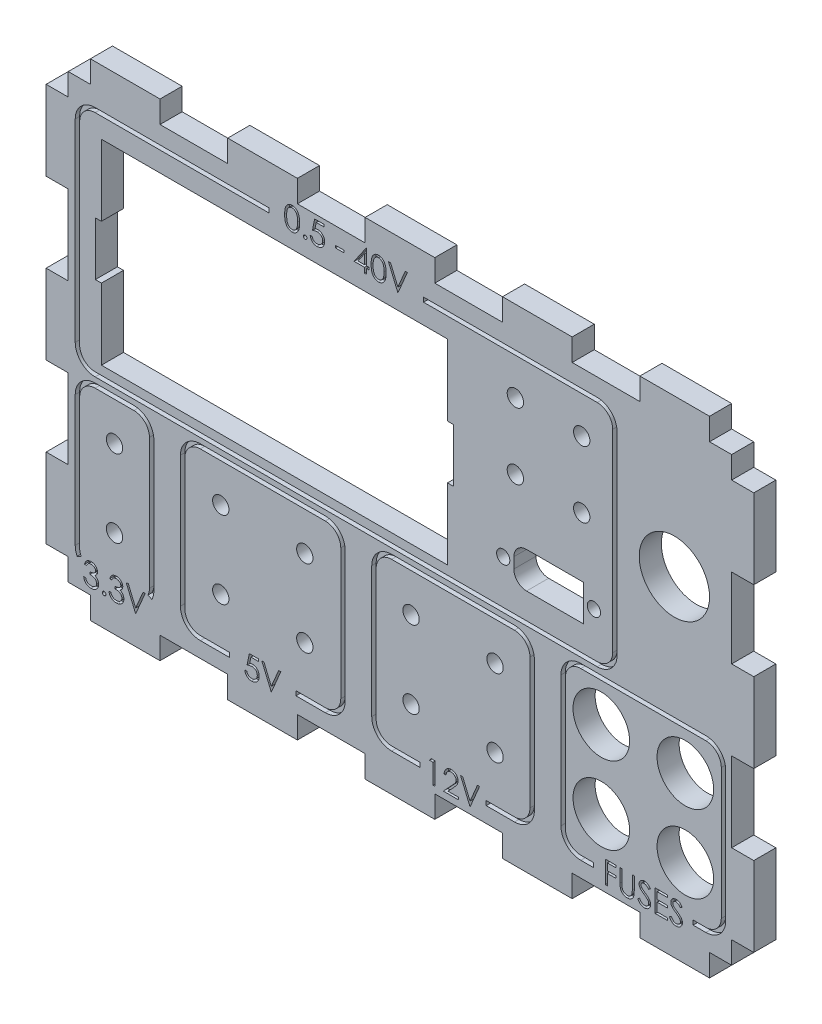
SolidWorks part; units mm, degrees
ref_plane "Front Plane" through (0, 0, 0) normal (0, 0, 1) x (1, 0, 0)
ref_plane "Top Plane" through (0, 0, 0) normal (0, 1, 0) x (1, 0, 0)
ref_plane "Right Plane" through (0, 0, 0) normal (1, 0, 0) x (0, 0, -1)
sketch "Sketch1" plane through (0, 0, 0) normal (0, 0, 1) x (1, 0, 0)
  line L1 (-75, 50) -> (-70, 50)
  line L2 (-75, 50) -> (-75, 45)
  line L3 (-75, -50) -> (-70, -50)
  line L4 (75, 50) -> (75, 45)
  line L5 (-75, 50) -> (75, -50) construction
  line L6 (-75, -50) -> (75, 50) construction
  line L7 (-75, 45) -> (-80, 45)
  line L9 (-75, 27) -> (-80, 27)
  line L10 (-80, 45) -> (-80, 27)
  line L11 (-75, 9) -> (-80, 9)
  line L12 (-80, 9) -> (-80, -9)
  line L13 (-75, -9) -> (-80, -9)
  line L15 (-75, -27) -> (-80, -27)
  line L16 (-80, -27) -> (-80, -45)
  line L17 (-75, -45) -> (-80, -45)
  line L18 (-80, -50) -> (-80, -45) construction
  line L19 (-80, 45) -> (-80, 50) construction
  line L20 (0, 55) -> (0, -55) construction
  line L21 (75, -27) -> (80, -27)
  line L22 (80, -27) -> (80, -45)
  line L23 (75, -45) -> (80, -45)
  line L25 (75, 9) -> (80, 9)
  line L26 (80, 9) -> (80, -9)
  line L27 (75, -9) -> (80, -9)
  line L29 (75, 27) -> (80, 27)
  line L30 (80, 45) -> (80, 27)
  line L31 (75, 45) -> (80, 45)
  line L33 (-38.9375, 50) -> (-38.9375, 55)
  line L35 (-70, 50) -> (-70, 55)
  line L36 (-70, 55) -> (-54.25, 55)
  line L37 (-54.25, 50) -> (-54.25, 55)
  line L39 (-23.1875, 50) -> (-23.1875, 55)
  line L40 (-38.9375, 55) -> (-23.1875, 55)
  line L41 (-7.875, 50) -> (-7.875, 55)
  line L43 (7.875, 50) -> (7.875, 55)
  line L44 (-7.875, 55) -> (7.875, 55)
  line L45 (23.1875, 50) -> (23.1875, 55)
  line L47 (38.9375, 50) -> (38.9375, 55)
  line L48 (23.1875, 55) -> (38.9375, 55)
  line L49 (54.25, 50) -> (54.25, 55)
  line L51 (70, 50) -> (70, 55)
  line L52 (54.25, 55) -> (70, 55)
  line L53 (-70, 55) -> (-75, 55) construction
  line L54 (70, 55) -> (75, 55) construction
  line L55 (-80, 0) -> (80, 0) construction
  line L57 (70, -50) -> (70, -55)
  line L58 (54.25, -55) -> (70, -55)
  line L59 (54.25, -50) -> (54.25, -55)
  line L61 (38.9375, -50) -> (38.9375, -55)
  line L62 (23.1875, -55) -> (38.9375, -55)
  line L63 (23.1875, -50) -> (23.1875, -55)
  line L65 (7.875, -50) -> (7.875, -55)
  line L66 (-7.875, -55) -> (7.875, -55)
  line L67 (-7.875, -50) -> (-7.875, -55)
  line L69 (-23.1875, -50) -> (-23.1875, -55)
  line L70 (-38.9375, -55) -> (-23.1875, -55)
  line L71 (-38.9375, -50) -> (-38.9375, -55)
  line L72 (-70, -55) -> (-54.25, -55)
  line L73 (-54.25, -50) -> (-54.25, -55)
  line L75 (-70, -50) -> (-70, -55)
  line L76 (-54.25, 50) -> (-38.9375, 50)
  line L77 (-23.1875, 50) -> (-7.875, 50)
  line L78 (7.875, 50) -> (23.1875, 50)
  line L79 (38.9375, 50) -> (54.25, 50)
  line L80 (70, 50) -> (75, 50)
  line L81 (75, 27) -> (75, 9)
  line L82 (75, -9) -> (75, -27)
  line L83 (75, -45) -> (75, -50)
  line L84 (70, -50) -> (75, -50)
  line L85 (38.9375, -50) -> (54.25, -50)
  line L86 (7.875, -50) -> (23.1875, -50)
  line L87 (-23.1875, -50) -> (-7.875, -50)
  line L88 (-54.25, -50) -> (-38.9375, -50)
  line L89 (-75, -45) -> (-75, -50)
  line L92 (-75, -9) -> (-75, -27)
  line L93 (-75, 27) -> (-75, 9)
  point P0 (0, 0)
  dimension "D1" = 150
  dimension "D2" = 100
  dimension "D3" = 5
  dimension "D4" = 5
  dimension "D5" = 18
  dimension "D7" = 15.75
  dimension "D8" = 5
  dimension "D9" = 5
  dimension "D6" = 3
  dimension "D10" = 5
extrude "Boss-Extrude1" add sketch "Sketch1" along normal blind 5 contours L4 L1 L2 L3 | L13 L11 L12 | L7 L10 L9 L2 | L1 L37 L36 L35 | L40 L33 L1 L39 | L44 L41 L1 L43 | L48 L45 L1 L47 | L52 L49 L1 L51 | L31 L4 L29 L30 | L4 L27 L26 L25 | L4 L23 L22 L21 | L3 L59 L58 L57 | L3 L63 L62 L61 | L3 L67 L66 L65 | L3 L71 L70 L69 | L3 L75 L72 L73 | L17 L2 L15 L16 region at (0, 0, 0)
sketch "Sketch2" plane through (0, 0, 5) normal (0, 0, 1) x (1, 0, 0)
  line L0 (-67.5, 40.5) -> (10.75, 40.5)
  line L1 (10.75, 40.5) -> (10.75, 24.425)
  line L2 (10.75, 24.425) -> (12.125, 24.425)
  line L3 (12.125, 24.425) -> (12.125, 12.325)
  line L4 (12.125, 12.325) -> (10.75, 12.325)
  line L5 (10.75, 12.325) -> (10.75, -3.75)
  line L6 (10.75, -3.75) -> (-67.5, -3.75)
  line L7 (-67.5, -3.75) -> (-67.5, 12.325)
  line L8 (-67.5, 12.325) -> (-68.875, 12.325)
  line L9 (-68.875, 12.325) -> (-68.875, 24.425)
  line L10 (-68.875, 24.425) -> (-67.5, 24.425)
  line L11 (-67.5, 24.425) -> (-67.5, 40.5)
  line L12 (-67.5, 40.5) -> (10.75, -3.75) construction
  line L13 (10.75, 40.5) -> (-67.5, -3.75) construction
  line L14 (75, 50) -> (75, 45) construction
  line L15 (-75, 50) -> (-70, 50) construction
  line L16 (28.62, 8.2375) -> (41.45, 8.2375)
  line L25 (41.45, 8.2375) -> (41.45, 0.0875)
  line L26 (41.45, 0.0875) -> (28.62, 0.0875)
  line L27 (25.75, 2.9575) -> (25.75, 5.3675)
  line L28 (25.75, 4.1625) -> (41.45, 4.1625) construction
  line L31 (23.35, 4.1625) -> (43.85, 4.1625) construction
  line L33 (26.1, 36.6625) -> (41.1, 21.6625) construction
  line L34 (33.6, 36.6625) -> (33.6, 0.0875) construction
  line L35 (-64.53, -17.625) -> (-64.53, -35.125) construction
  line L36 (75, -45) -> (75, -50) construction
  line L37 (-75, 50) -> (-75, 45) construction
  line L38 (-75, -45) -> (-75, -50) construction
  line L39 (41.1, 21.6625) -> (75, 21.6625) construction
  line L44 (-67.5, -3.75) -> (-67.5, -50) construction
  line L45 (-75, -50) -> (-70, -50) construction
  circle A0 centre (-64.53, -17.625) radius 1.85
  circle A1 centre (-40.51, -17.625) radius 1.85
  circle A2 centre (2.51, -17.625) radius 1.85
  circle A3 centre (-64.53, -35.125) radius 1.85
  circle A4 centre (-21.51, -17.625) radius 1.85
  circle A5 centre (-21.51, -35.125) radius 1.85
  circle A6 centre (-40.51, -35.125) radius 1.85
  circle A7 centre (21.51, -17.625) radius 1.85
  circle A8 centre (21.51, -35.125) radius 1.85
  circle A9 centre (2.51, -35.125) radius 1.85
  circle A10 centre (26.1, 36.6625) radius 1.85
  circle A11 centre (41.1, 36.6625) radius 1.85
  circle A12 centre (41.1, 21.6625) radius 1.85
  circle A13 centre (26.1, 21.6625) radius 1.85
  circle A14 centre (23.35, 4.1625) radius 1.5
  circle A15 centre (43.85, 4.1625) radius 1.5
  arc A16 (28.62, 0.0875) -> (25.75, 2.9575) centre (28.62, 2.9575) cw
  arc A17 (25.75, 5.3675) -> (28.62, 8.2375) centre (28.62, 5.3675) cw
  circle A19 centre (45.53, -17.625) radius 6.4
  circle A20 centre (64.53, -17.625) radius 6.4
  circle A21 centre (64.53, -35.125) radius 6.4
  circle A22 centre (45.53, -35.125) radius 6.4
  point P8 (-68.875, 18.375)
  point P13 (-28.375, 18.375)
  point P57 (33.6, 4.1625)
  point P59 (33.6, 4.1625)
  point P61 (41.45, 4.1625)
  point P63 (33.6, 29.1625)
  point P68 (33.6, 18.375)
  point P69 (12.125, 18.375)
  point P78 (-64.53, -26.375)
  point P90 (-67.5, -26.875)
  dimension "D7" = 3.7
  dimension "D8" = 2
  dimension "D22" = 3
  dimension "D25" = 15.7
  dimension "D28" = 0.5
  dimension "D33" = 2
  dimension "D13" = 12.8
  dimension "D1" = 78.25
  dimension "D2" = 81
  dimension "D3" = 44.25
  dimension "D4" = 12.1
  dimension "D5" = 9.5
  dimension "D6" = 7.5
  dimension "D14" = 19
  dimension "D15" = 17.5
  dimension "D16" = 19
  dimension "D17" = 2
  dimension "D20" = 15
  dimension "D21" = 15
  dimension "D23" = 12.83
  dimension "D24" = 8.15
  dimension "D26" = 20.5
  dimension "D27" = 15
  dimension "D29" = 17.5
  dimension "D30" = 10.47
  dimension "D31" = 24.02
  dimension "D32" = 24.02
  dimension "D34" = 10.47
  dimension "D35" = 19
  dimension "D9" = 2
  dimension "D10" = 2
  dimension "D11" = 2
  dimension "D12" = 2
  dimension "D18" = 2
  dimension "D19" = 2
extrude "Cut-Extrude1" cut sketch "Sketch2" against normal blind 5
sketch "Sketch3" plane through (0, 0, 5) normal (0, 0, 1) x (1, 0, 0)
  line L0 (-64.53, -35.125) -> (-64.53, -17.625) construction
  line L1 (-68.92, 45.5) -> (-29.66, 45.5)
  line L2 (-72.92, 41.5) -> (-72.92, -2.25)
  line L3 (-68.92, -6.25) -> (44.6, -6.25)
  line L4 (48.6, 41.5) -> (48.6, -2.25)
  line L5 (-68.92, -8.455) -> (-60.14, -8.455)
  line L6 (-72.92, -12.455) -> (-72.92, -42)
  line L8 (-56.14, -12.455) -> (-56.14, -42)
  line L9 (-45.14, -8.455) -> (-16.88, -8.455)
  line L10 (-49.14, -12.455) -> (-49.14, -42)
  line L11 (-45.14, -46) -> (-38.51, -46)
  line L12 (-12.88, -12.455) -> (-12.88, -42)
  line L13 (-1.88, -8.455) -> (25.9, -8.455)
  line L14 (-5.88, -12.455) -> (-5.88, -42)
  line L15 (-1.88, -46) -> (4.51, -46)
  line L16 (29.9, -12.455) -> (29.9, -42)
  line L17 (40.9, -8.455) -> (69.16, -8.455)
  line L18 (36.9, -12.455) -> (36.9, -42)
  line L19 (40.9, -46) -> (43.78, -46)
  line L20 (73.16, -12.455) -> (73.16, -42)
  line L21 (-40.51, -17.625) -> (-21.51, -35.125) construction
  line L22 (21.51, -17.625) -> (2.51, -35.125) construction
  line L24 (10.75, 40.5) -> (-67.5, 40.5) construction
  line L25 (-67.5, -3.75) -> (10.75, -3.75) construction
  line L26 (-68.92, -46) -> (-60.14, -46) construction
  line L27 (45.53, -17.625) -> (64.53, -35.125) construction
  line L28 (-71.8247, 44.25) -> (47.5047, 44.25) construction
  line L29 (-72.53, -43.7228) -> (-56.53, -43.7228) construction
  line L30 (-38.51, -46) -> (-23.51, -46) construction
  line L31 (4.51, -46) -> (19.51, -46) construction
  line L32 (43.78, -46) -> (66.28, -46) construction
  line L33 (-23.51, -46) -> (-16.88, -46)
  line L34 (19.51, -46) -> (25.9, -46)
  line L35 (66.28, -46) -> (69.16, -46)
  line L36 (-75, -50) -> (-70, -50) construction
  line L37 (-29.66, 45.5) -> (5.34, 45.5) construction
  line L38 (5.34, 45.5) -> (44.6, 45.5)
  circle A0 centre (41.1, 36.6625) radius 1.85 construction
  circle A1 centre (41.1, 36.6625) radius 1.85
  arc A2 (-72.92, -2.25) -> (-68.92, -6.25) centre (-68.92, -2.25) ccw
  arc A3 (44.6, -6.25) -> (48.6, -2.25) centre (44.6, -2.25) ccw
  arc A4 (44.6, 45.5) -> (48.6, 41.5) centre (44.6, 41.5) cw
  arc A5 (-68.92, 45.5) -> (-72.92, 41.5) centre (-68.92, 41.5) ccw
  arc A6 (36.9, -42) -> (40.9, -46) centre (40.9, -42) ccw
  arc A7 (69.16, -46) -> (73.16, -42) centre (69.16, -42) ccw
  arc A8 (69.16, -8.455) -> (73.16, -12.455) centre (69.16, -12.455) cw
  arc A9 (40.9, -8.455) -> (36.9, -12.455) centre (40.9, -12.455) ccw
  arc A10 (25.9, -8.455) -> (29.9, -12.455) centre (25.9, -12.455) cw
  arc A11 (25.9, -46) -> (29.9, -42) centre (25.9, -42) ccw
  arc A12 (-5.88, -42) -> (-1.88, -46) centre (-1.88, -42) ccw
  arc A13 (-1.88, -8.455) -> (-5.88, -12.455) centre (-1.88, -12.455) ccw
  arc A14 (-45.14, -8.455) -> (-49.14, -12.455) centre (-45.14, -12.455) ccw
  arc A15 (-16.88, -8.455) -> (-12.88, -12.455) centre (-16.88, -12.455) cw
  arc A16 (-16.88, -46) -> (-12.88, -42) centre (-16.88, -42) ccw
  arc A17 (-49.14, -42) -> (-45.14, -46) centre (-45.14, -42) ccw
  arc A18 (-72.92, -42) -> (-72.53, -43.7228) centre (-68.92, -42) ccw
  arc A19 (-56.53, -43.7228) -> (-56.14, -42) centre (-60.14, -42) ccw
  arc A20 (-60.14, -8.455) -> (-56.14, -12.455) centre (-60.14, -12.455) cw
  arc A21 (-68.92, -8.455) -> (-72.92, -12.455) centre (-68.92, -12.455) ccw
  arc A22 (-56.14, -42) -> (-60.14, -46) centre (-60.14, -42) cw
  arc A23 (-72.92, -42) -> (-68.92, -46) centre (-68.92, -42) ccw
  point P26 (-64.53, -8.455)
  point P35 (-31.01, -26.375)
  point P36 (-31.01, -8.455)
  point P37 (12.01, -26.375)
  point P38 (12.01, -8.455)
  point P58 (55.03, -8.455)
  point P59 (55.03, -26.375)
  point P103 (-31.01, -46)
  point P106 (12.01, -46)
  point P109 (55.03, -46)
  point P115 (-12.16, 45.5)
  dimension "D5" = 4
  dimension "D11" = 4
  dimension "D18" = 35
  dimension "D2" = 5
  dimension "D3" = 2.5
  dimension "D4" = 7.5
  dimension "D6" = 7
  dimension "D7" = 16.78
  dimension "D8" = 9.17
  dimension "D9" = 4
  dimension "D10" = 7
  dimension "D12" = 2.5
  dimension "D13" = 16
  dimension "D14" = 22.5
  dimension "D15" = 15
  dimension "D16" = 15
  dimension "D17" = 7
extrude "Cut-Extrude-Thin1" cut sketch "Sketch3" against normal blind 1 thin contours L38 A4 L4 A3 L3 A2 L2 A5 L1 | L6 A21 L5 A20 L8 | A19 | A18 | L33 A16 L12 A15 L9 A14 L10 A17 L11 | L34 A11 L16 A10 L13 A13 L14 A12 L15 | L35 A7 L20 A8 L17 A9 L18 A6 L19 thin type mid plane wall 1
sketch "Sketch4" plane through (0, 0, 5) normal (0, 0, 1) x (1, 0, 0)
  line L0 (-72.6617, 44) -> (48.3417, 44) construction
  line L1 (-29.66, 46) -> (-68.92, 46) construction
  line L2 (-72.42, -48.5) -> (-56.64, -48.5) construction
  line L3 (-49.64, -48.5) -> (-12.38, -48.5) construction
  line L4 (-6.38, -48.5) -> (30.4, -48.5) construction
  line L5 (36.4, -48.5) -> (73.66, -48.5) construction
  line L7 (-56.64, -39.1716) -> (-56.64, -12.455) construction
  line L8 (-72.42, -12.455) -> (-72.42, -44.8284) construction
  line L109 (-49.64, -12.455) -> (-49.64, -42) construction
  line L110 (-12.38, -42) -> (-12.38, -12.455) construction
  line L111 (-45.14, -46.5) -> (-38.51, -46.5) construction
  line L112 (30.4, -42) -> (30.4, -12.455) construction
  line L113 (-6.38, -12.455) -> (-6.38, -42) construction
  line L114 (73.66, -42) -> (73.66, -12.455) construction
  line L115 (36.4, -12.455) -> (36.4, -42) construction
  arc A0 (-68.92, 46) -> (-73.42, 41.5) centre (-68.92, 41.5) ccw construction
  arc A1 (49.1, 41.5) -> (44.6, 46) centre (44.6, 41.5) ccw construction
  text T0 "3.3V" font "Century Gothic" height 5
  text T1 "5V" font "Century Gothic" height 5
  text T2 "12V" font "Century Gothic" height 5
  text T3 "FUSES" font "Century Gothic" height 5
  text T4 "0.5 - 40V" font "Century Gothic" height 5
  dimension "D1" = 2
  dimension "D2" = 2
extrude "Cut-Extrude2" cut sketch "Sketch4" against normal blind 1
sketch "Sketch5" plane through (0, 0, 5) normal (0, 0, 1) x (1, 0, 0)
  line L0 (49.1, 19.625) -> (75, 19.625) construction
  line L1 (49.1, 41.5) -> (49.1, -2.25) construction
  line L2 (75, 27) -> (75, 9) construction
  circle A0 centre (62.05, 19.625) radius 7.95
  point P9 (62.05, 19.625)
  dimension "D1" = 15.9
extrude "Cut-Extrude3" cut sketch "Sketch5" against normal through all
